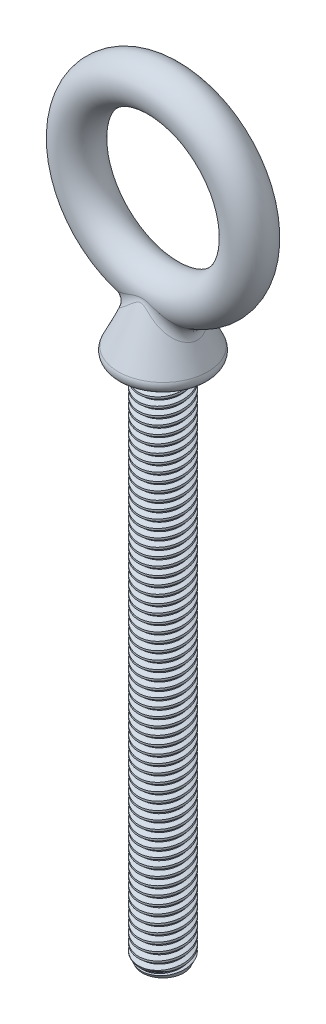
SolidWorks part; units mm, degrees
ref_plane "Front" through (0, 0, 0) normal (0, 0, 1) x (1, 0, 0)
ref_plane "Top" through (0, 0, 0) normal (0, 1, 0) x (1, 0, 0)
ref_plane "Right" through (0, 0, 0) normal (1, 0, 0) x (0, 0, -1)
sketch "Sketch1" plane through (0, 0, 0) normal (-1, 0, 0) x (0, 1, 0)
  line L0 (-21.0344, 0) -> (-12.7, 0) construction
  line L1 (-12.7, 0) -> (0, 0) construction
  line L2 (0, 10.2426) -> (0, -9.3978) construction
  circle A0 centre (-16.8672, 0) radius 4.1672
  circle A1 centre (16.8672, 0) radius 4.1672 construction
  dimension "D1" = 8.3344
  dimension "D3" = 8.3344
  dimension "Eye OD" = 42.0688
  dimension "Eye ID" = 25.4
revolve "Revolve1" add sketch "Sketch1" angle 360 about L2
sketch "Sketch3" plane through (0, 0, 0) normal (1, 0, 0) x (0, 0, -1)
  line L0 (-4.1672, -16.8672) -> (-8.7398, -26.6868)
  line L1 (-7.2832, -28.9719) -> (-4.7625, -28.9719)
  line L2 (0, -130.5719) -> (0, -16.8672)
  line L3 (0, -16.8672) -> (-4.1672, -16.8672)
  line L4 (0, 0) -> (0, -80.8733) construction
  line L5 (-4.7625, -28.9719) -> (-4.7625, -130.5719)
  line L6 (-4.7625, -130.5719) -> (0, -130.5719)
  line L7 (-7.2832, -28.9719) -> (-9.8039, -28.9719) construction
  line L8 (-9.8039, -28.9719) -> (-8.7398, -26.6868) construction
  line L9 (4.7625, -28.9719) -> (4.7625, -130.5719) construction
  arc A0 (-8.7398, -26.6868) -> (-7.2832, -28.9719) centre (-7.2832, -27.3651) ccw
  circle A1 centre (0, -16.8672) radius 4.1672 construction
  circle A2 centre (0, 16.8672) radius 4.1672 construction
  dimension "Shoulder Dia" = 17.78
  dimension "Thread Dia" = 9.525
  dimension "Overall Length" = 151.6062
  dimension "Shank Length" = 101.6
revolve "Revolve2" add sketch "Sketch3" angle 360 about L4
fillet "Fillet1" radius 2.0836 1 edges at (4.5198, -19.39, 2.8475)
sketch "Sketch4" plane through (0, 0, 0) normal (1, 0, 0) x (0, 0, -1)
  line L0 (-4.7625, -28.9719) -> (4.7625, -28.9719) construction
  line L1 (4.7625, -28.9719) -> (4.7951, -29.1676) construction
  line L2 (4.7951, -29.1676) -> (5.0235, -30.5378)
  line L3 (5.0235, -30.5378) -> (4.0944, -30.1897)
  line L4 (4.0944, -30.1897) -> (4.0291, -29.7982)
  line L5 (4.0291, -29.7982) -> (4.7951, -29.1676)
  line L6 (4.9093, -29.8527) -> (4.0617, -29.994) construction
  line L7 (-4.7625, -28.9719) -> (-4.7625, -30.5594) construction
  line L8 (-4.7625, -30.5594) -> (4.7625, -28.9719) construction
  line L9 (-4.7625, -28.9719) -> (-4.7625, -130.5719) construction
  line L10 (4.7625, -28.9719) -> (4.7625, -130.5719) construction
  line L12 (-4.7625, -31.4647) -> (4.7625, -29.8772) construction
  line L13 (-0.2832, -28.9719) -> (0.2832, -32.3699) construction
  line L15 (-4.7625, -130.5719) -> (0, -130.5719) construction
  point P19 (0, -30.6709)
  dimension "D1" = 60
  dimension "D2" = 0.1984
  dimension "Thread Pitch" = 1.5875
  dimension "D3" = 0.3969
  dimension "D4" = 1.5875
  dimension "Thread Length" = 101.6
revolve "Cut-Revolve1" cut sketch "Sketch4" angle 360 about L13
sketch "Sketch5" plane through (0, 0, 0) normal (1, 0, 0) x (0, 0, -1)
  line L0 (4.0291, -130.5719) -> (4.7625, -130.5719)
  line L1 (4.7625, -130.5719) -> (4.7625, -128.9991)
  line L2 (4.7625, -128.9991) -> (4.0291, -130.5719)
  line L3 (4.7625, -28.9719) -> (4.7625, -130.5719) construction
  line L4 (-4.7625, -130.5719) -> (0, -130.5719) construction
  line L5 (0, 0) -> (0, -130.5719) construction
  dimension "D1" = 25
revolve "Cut-Revolve2" cut sketch "Sketch5" angle 360 about L5
pattern_linear "LPattern1" count 64 spacing 1.5875 along (0, -1, 0) of "Cut-Revolve1"
sketch "Sketch6" plane through (0, 0, 0) normal (0, 0, 1) x (1, 0, 0)
  line L0 (-21.0344, 0) -> (-12.7, 0)
  line L1 (12.7, 0) -> (21.0344, 0)
  arc A0 (21.0344, 0) -> (-21.0344, 0) centre (0, 0) ccw
  arc A1 (12.7, 0) -> (-12.7, 0) centre (0, 0) ccw
  dimension "hex flats" = 14.2748
  dimension "hex flats/2" = 7.366
equation "\"D1@Fillet1\"=\"D3@Sketch1\"/4"
equation "\"D2@Sketch4\"=\"Thread Pitch@Sketch4\"/8"
equation "\"D3@Sketch4\"=\"Thread Pitch@Sketch4\"/4"
equation "\"D4@Sketch4\"=\"Thread Pitch@Sketch4\""
equation "\"D3@LPattern1\"=\"Thread Pitch@Sketch4\""
equation "\"D1@LPattern1\"=\"Thread Length@Sketch4\"/\"Thread Pitch@Sketch4\""
